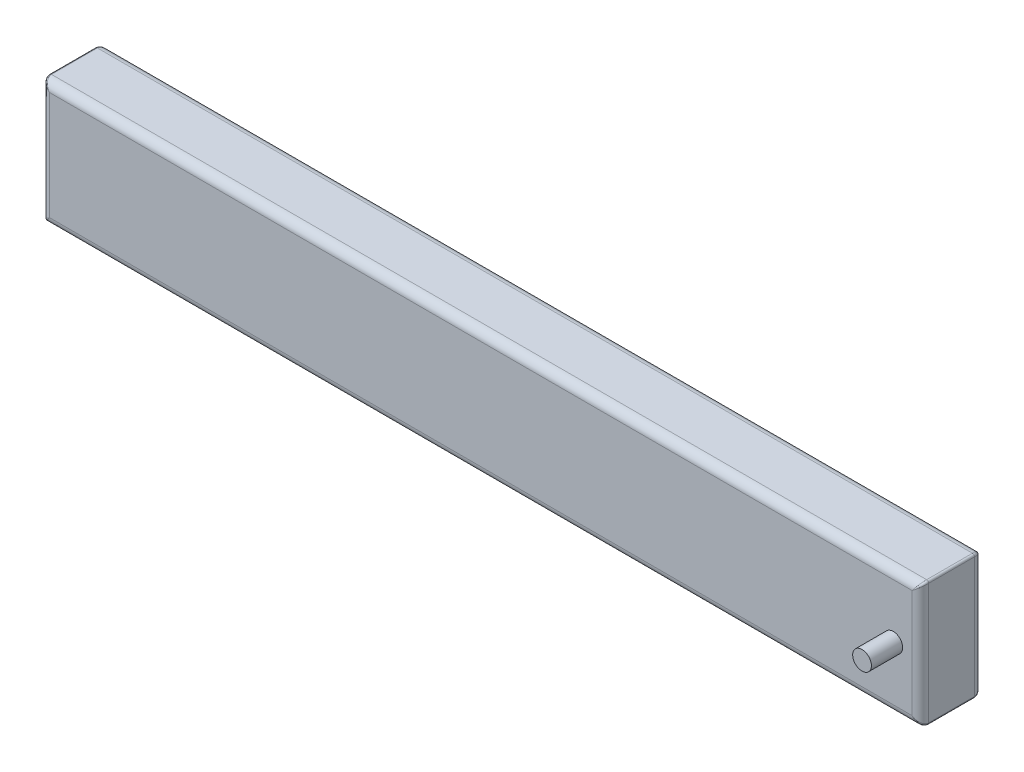
SolidWorks part; units mm, degrees
ref_plane "Front Plane" through (0, 0, 0) normal (0, 0, 1) x (1, 0, 0)
ref_plane "Top Plane" through (0, 0, 0) normal (0, 1, 0) x (1, 0, 0)
ref_plane "Right Plane" through (0, 0, 0) normal (1, 0, 0) x (0, 0, -1)
sketch "Sketch1" plane through (0, 0, 0) normal (0, 0, 1) x (1, 0, 0)
  line L1 (10, 0) -> (4210, 0)
  line L2 (0, -10) -> (0, -590)
  line L3 (10, -600) -> (4210, -600)
  line L4 (4220, -10) -> (4220, -590)
  arc A0 (4210, -600) -> (4220, -590) centre (4210, -590) ccw
  arc A1 (0, -590) -> (10, -600) centre (10, -590) ccw
  arc A2 (10, 0) -> (0, -10) centre (10, -10) ccw
  arc A3 (4210, 0) -> (4220, -10) centre (4210, -10) cw
  point P11 (0, 0)
  dimension "D1" = 10
  dimension "D2" = 4200
  dimension "D3" = 600
extrude "Boss-Extrude1" add sketch "Sketch1" along normal blind 300
fillet "Fillet1" radius 40 16 edges at (0, -300, 300) (2110, 0, 300) (4220, -300, 300) (2110, -600, 300) (0, -300, 0) (2110, 0, 0) (4220, -300, 0) (2110, -600, 0) (2.9289, -2.9289, 300) (2.9289, -2.9289, 0) (4217.0711, -2.9289, 300) (4217.0711, -2.9289, 0) (4217.0711, -597.0711, 300) (4217.0711, -597.0711, 0) (2.9289, -597.0711, 300) (2.9289, -597.0711, 0)
sketch "Sketch2" plane through (0, 0, 300) normal (0, 0, 1) x (1, 0, 0)
  line L0 (4180, -560) -> (4180, -40) construction
  circle A0 centre (4090, -300) radius 45
  dimension "D1" = 90
  dimension "D2" = 90
extrude "Boss-Extrude2" add sketch "Sketch2" along normal blind 150
